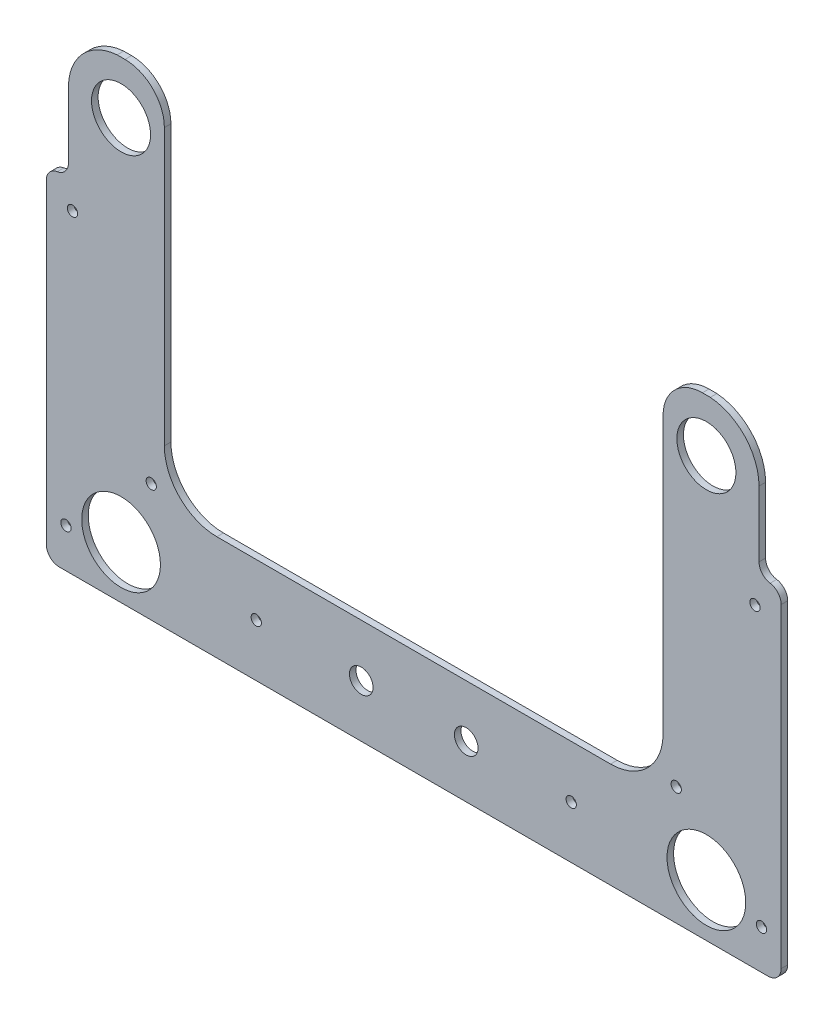
SolidWorks part; units mm, degrees
material "6061 Alloy"
ref_plane "Front Plane" through (0, 0, 0) normal (0, 0, 1) x (1, 0, 0)
ref_plane "Top Plane" through (0, 0, 0) normal (0, 1, 0) x (1, 0, 0)
ref_plane "Right Plane" through (0, 0, 0) normal (1, 0, 0) x (0, 0, -1)
sketch "Sketch1" plane through (0, 0, 0) normal (0, 0, 1) x (1, 0, 0)
  line L5 (120.65, -152.4) -> (120.65, -6.35)
  line L6 (127, 0) -> (171.45, 0) construction
  line L7 (177.8, -6.35) -> (177.8, -222.25)
  line L10 (0, -206.2199) -> (0, -63.6275) construction
  line L11 (-54.9244, 0) -> (300.6756, 0) construction
  line L13 (12.7, -177.8) -> (95.25, -177.8)
  line L14 (12.7, -228.6) -> (171.45, -228.6)
  line L15 (141.605, -25.4) -> (141.605, -84.2822) construction
  line L16 (141.605, -25.4) -> (141.605, -127) construction
  line L19 (-141.605, -19.05) -> (-141.605, -77.9322) construction
  line L20 (141.605, -25.4) -> (141.605, -203.2) construction
  line L22 (-120.65, -152.4) -> (-120.65, -6.35)
  line L23 (-12.7, -177.8) -> (-95.25, -177.8)
  line L24 (-12.7, -228.6) -> (-171.45, -228.6)
  line L25 (-177.8, -6.35) -> (-177.8, -222.25)
  line L26 (-12.7, -177.8) -> (12.7, -177.8)
  line L27 (-12.7, -228.6) -> (12.7, -228.6)
  line L28 (-177.8, -6.35) -> (-177.8, 6.35)
  line L29 (-165.1, 19.05) -> (-133.35, 19.05)
  line L30 (-120.65, 6.35) -> (-120.65, -6.35)
  line L31 (120.65, 6.35) -> (120.65, -6.35)
  line L32 (177.8, -6.35) -> (177.8, 6.35)
  line L33 (165.1, 19.05) -> (133.35, 19.05)
  arc A0 (95.25, -177.8) -> (120.65, -152.4) centre (95.25, -152.4) ccw
  arc A4 (120.65, -6.35) -> (127, 0) centre (127, -6.35) cw construction
  circle A8 centre (141.605, -25.4) radius 14.2875
  circle A9 centre (141.605, -25.4) radius 38.1 construction
  arc A10 (177.8, -6.35) -> (171.45, 0) centre (171.45, -6.35) ccw construction
  arc A11 (171.45, -228.6) -> (177.8, -222.25) centre (171.45, -222.25) ccw
  arc A14 (141.605, -82.55) -> (120.9214, -78.6758) centre (141.605, -25.4) ccw construction
  arc A15 (-141.605, -82.55) -> (-120.9214, -78.6758) centre (-141.605, -25.4) cw construction
  circle A16 centre (-141.605, -25.4) radius 38.1 construction
  circle A17 centre (-141.605, -25.4) radius 14.2875
  arc A19 (-95.25, -177.8) -> (-120.65, -152.4) centre (-95.25, -152.4) cw
  circle A20 centre (141.605, -127) radius 38.1 construction
  circle A21 centre (-141.605, -127) radius 38.1 construction
  arc A23 (-171.45, -228.6) -> (-177.8, -222.25) centre (-171.45, -222.25) cw
  circle A24 centre (-141.605, -203.2) radius 19.05
  circle A37 centre (141.605, -203.2) radius 19.05
  circle A39 centre (-76.2, -203.2) radius 2.4892
  circle A40 centre (76.2, -203.2) radius 2.4892
  circle A42 centre (-25.4, -203.2) radius 5.715
  arc A44 (-133.35, 19.05) -> (-120.65, 6.35) centre (-133.35, 6.35) cw
  arc A45 (-177.8, 6.35) -> (-165.1, 19.05) centre (-165.1, 6.35) cw
  arc A46 (133.35, 19.05) -> (120.65, 6.35) centre (133.35, 6.35) ccw
  arc A47 (177.8, 6.35) -> (165.1, 19.05) centre (165.1, 6.35) ccw
  circle A50 centre (-149.225, 6.35) radius 2.4892
  circle A53 centre (149.225, 6.35) radius 2.4892
  circle A54 centre (-168.275, -209.55) radius 2.4892
  circle A56 centre (168.275, -209.55) radius 2.4892
  circle A58 centre (-165.1, -76.2) radius 2.4892
  circle A59 centre (165.1, -76.2) radius 2.4892
  circle A60 centre (-127, -171.45) radius 2.4892
  circle A61 centre (127, -171.45) radius 2.4892
  circle A62 centre (25.4, -203.2) radius 5.715
  point P2 (177.8, -44.45)
  point P18 (177.8, 0)
  point P23 (177.8, -228.6)
  point P24 (177.8, -228.6)
  point P31 (177.8, 0)
  point P48 (-177.8, 0)
  point P49 (-177.8, -228.6)
  point P51 (-177.8, -44.45)
  point P78 (-141.605, -203.2)
  dimension "D6" = 25.4
  dimension "D7" = 6.35
  dimension "D8" = 6.35
  dimension "D9" = 177.8
  dimension "D10" = 28.575
  dimension "D12" = 76.2
  dimension "D13" = 57.15
  dimension "D15" = 38.1
  dimension "D18" = 76.2
  dimension "D21" = 4.9784
  dimension "D29" = 9.525
  dimension "D32" = 4.9784
  dimension "D35" = 11.43
  dimension "D40" = 12.7
  dimension "D43" = 4.9784
  dimension "D45" = 12.7
  dimension "D30" = 4.9784
  dimension "D41" = 4.9784
  dimension "D22" = 6.35
  dimension "D2" = 120.65
  dimension "D3" = 177.8
  dimension "D4" = 228.6
  dimension "D5" = 177.8
  dimension "D11" = 20.955
  dimension "`" = 25.4
  dimension "D14" = 57.15
  dimension "D16" = 184.15
  dimension "D17" = 101.6
  dimension "D19" = 25.4
  dimension "D20" = 101.6
  dimension "D23" = 57.15
  dimension "D25" = 25.4
  dimension "D26" = 19.05
  dimension "D27" = 25.4
  dimension "D28" = 25.4
  dimension "D31" = 25.4
  dimension "D33" = 12.7
  dimension "D34" = 25.4
  dimension "D39" = 19.05
  dimension "D44" = 28.575
  dimension "D24" = 95.25
extrude "Boss-Extrude3" add sketch "Sketch1" along normal blind 3.175
sketch "Sketch2" plane through (0, 0, 3.175) normal (0, 0, 1) x (1, 0, 0)
  line L0 (177.8, -222.25) -> (177.8, 6.35) construction
  line L1 (-177.8, 19.05) -> (177.8, 19.05)
  line L2 (-177.8, 19.05) -> (-177.8, 0)
  line L3 (-177.8, 0) -> (177.8, 0)
  line L4 (177.8, 19.05) -> (177.8, 0)
  line L5 (-177.8, 6.35) -> (-177.8, -222.25) construction
  line L7 (-133.35, 19.05) -> (-165.1, 19.05) construction
  dimension "D1" = 19.05
extrude "Cut-Extrude1" cut sketch "Sketch2" against normal through all
fillet "Fillet1" radius 19.05 4 edges at (177.8, 0, 1.5875) (120.65, 0, 1.5875) (-120.65, 0, 1.5875) (-177.8, 0, 1.5875)
sketch "Sketch3" plane through (0, 0, 3.175) normal (0, 0, 1) x (1, 0, 0)
  line L0 (-167.0763, -25.4) -> (-167.0763, -57.15)
  line L1 (-173.4263, -63.5) -> (-177.8, -63.5)
  line L2 (-177.8, -19.05) -> (-177.8, -222.25) construction
  line L3 (-158.75, 0) -> (-139.7, 0) construction
  line L4 (-177.8, -63.5) -> (-177.8, 0)
  line L5 (-177.8, 0) -> (-139.7, 0)
  arc A3 (-139.7, 0) -> (-167.0763, -25.4) centre (-141.605, -25.4) ccw
  arc A4 (-167.0763, -57.15) -> (-173.4263, -63.5) centre (-173.4263, -57.15) cw
  arc M14 (-158.75, 0) -> (-177.8, -19.05) centre (-158.75, -19.05) ccw
  line M15 (-177.8, -19.05) -> (-177.8, -222.25)
  dimension "D1" = 63.5
  dimension "D2" = 6.35
extrude "Cut-Extrude2" cut sketch "Sketch3" against normal through all contours A4 L0 A3 L5 L1 M14 M15 | L5 L4 M14 region at (-170.306, -29.421, 3.175) region at (-173.5448, -4.2552, 3.175)
ref_plane "Plane1" through (0, 0, 0) normal (-1, 0, 0) x (0, 0, 1)
mirror "Mirror1" about plane through (0, 0, 0) normal (-1, 0, 0) of "Cut-Extrude2"
fillet "Fillet2" radius 6.35 2 edges at (177.8, -63.5, 1.5875) (-177.8, -63.5, 1.5875)
